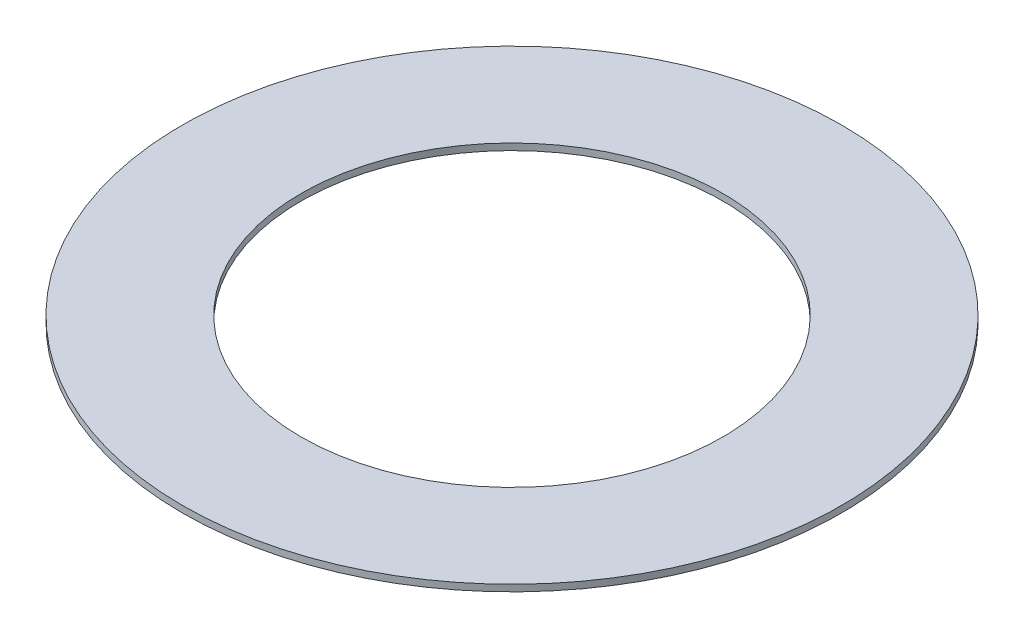
SolidWorks part; units mm, degrees
ref_plane "Front Plane" through (0, 0, 0) normal (0, 0, 1) x (1, 0, 0)
ref_plane "Top Plane" through (0, 0, 0) normal (0, 1, 0) x (1, 0, 0)
ref_plane "Right Plane" through (0, 0, 0) normal (1, 0, 0) x (0, 0, -1)
sketch "Sketch1" plane through (0, 0, 0) normal (0, 0, 1) x (1, 0, 0)
  line L0 (0, 0.7937) -> (0, -0.7937)
  line L1 (-152.4, 0) -> (152.4, 0) construction
  point P6 (0, 0)
  dimension "Width" = 304.8
  dimension "Thk" = 1.5875
sketch "Sketch2" plane through (0, 0, 0) normal (1, 0, 0) x (0, 0, -1)
  line L0 (152.4, 0) -> (-152.4, 0)
  point P4 (0, 0)
  dimension "Length" = 304.8
sketch "Sketch3" plane through (0, 0, 0) normal (0, 0, 1) x (1, 0, 0)
  line L1 (152.4, 0.7937) -> (-152.4, 0.7937)
  line L2 (152.4, 0.7937) -> (152.4, -0.7937)
  line L3 (152.4, -0.7937) -> (-152.4, -0.7937)
  line L4 (-152.4, 0.7937) -> (-152.4, -0.7937)
  line L5 (152.4, 0.7937) -> (-152.4, -0.7937) construction
  line L6 (152.4, -0.7937) -> (-152.4, 0.7937) construction
  point P0 (0, 0)
extrude "Boss-Extrude1" add sketch "Sketch3" along normal up to vertex (152.4 mm away) and the other way up to vertex (152.4 mm away) up to point (0, 0, 152.4) other way up to point (0, 0, -152.4)
sketch "Sketch4" plane through (0, 0.7937, 0) normal (0, 1, 0) x (1, 0, 0)
  circle A0 centre (0, 0) radius 79.375
  circle A1 centre (0, 0) radius 297.3401
  circle A2 centre (0, 0) radius 50.8
  line M3 (152.4, -152.4) -> (152.4, 152.4)
  line M4 (152.4, 152.4) -> (-152.4, 152.4)
  line M5 (-152.4, 152.4) -> (-152.4, -152.4)
  line M6 (-152.4, -152.4) -> (152.4, -152.4)
  dimension "D1" = 158.75
  dimension "D2" = 101.6
extrude "Cut-Extrude1" cut sketch "Sketch4" against normal blind 2.54 contours A0 M6 M3 M4 M5 | A2 region at (0, 0.7937, 0) region at (0, 0.7937, 148.0895)
